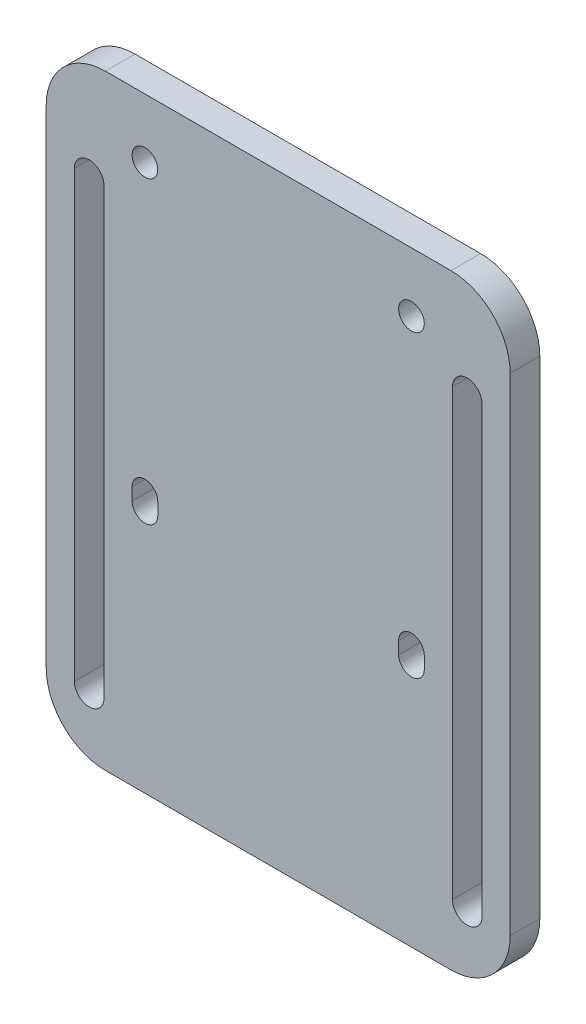
SolidWorks part; units mm, degrees
material "Acrylic (Medium-high impact)"
ref_plane "Спереди" through (0, 0, 0) normal (0, 0, 1) x (1, 0, 0)
ref_plane "Сверху" through (0, 0, 0) normal (0, 1, 0) x (1, 0, 0)
ref_plane "Справа" through (0, 0, 0) normal (1, 0, 0) x (0, 0, -1)
sketch "Model" plane through (0, 0, 0) normal (0, 0, 1) x (1, 0, 0)
  line L0 (0, 130.393) -> (0, -19.607) construction
  line L1 (38.3, 119.0065) -> (38.3, 3.8567) construction
  line L2 (39.6393, 110.7) -> (20.3566, 110.7) construction
  line L3 (27, 114.3973) -> (27, 106.7903) construction
  line L8 (27, 57.0366) -> (27, 46.0463) construction
  line L14 (-27, 114.3973) -> (-27, 106.7903) construction
  line L15 (-39.6393, 110.7) -> (-20.3566, 110.7) construction
  line L16 (-29.6, 50) -> (-29.6, 52.5)
  line L17 (-29.6, 52.5) -> (-29.6, 50)
  line L18 (-27, 57.0366) -> (-27, 46.0463) construction
  line L19 (-24.4, 52.5) -> (-24.4, 50)
  line L20 (-24.4, 50) -> (-24.4, 52.5)
  line L22 (-41.3, 12.5) -> (-41.3, 102.5)
  line L23 (-41.3, 102.5) -> (-41.3, 12.5)
  line L24 (-38.3, 119.0065) -> (-38.3, 3.8567) construction
  line L25 (-35.3, 102.5) -> (-35.3, 12.5)
  line L26 (-35.3, 12.5) -> (-35.3, 102.5)
  line L29 (-41.3, 12.5) -> (-35.3, 12.5) construction
  line L2974 (29.6, 52.5) -> (29.6, 50)
  line L2987 (24.4, 50) -> (24.4, 52.5)
  line L2994 (35.3, 12.5) -> (35.3, 102.5)
  line L3007 (41.3, 102.5) -> (41.3, 12.5)
  line L3504 (35, 0) -> (-35, 0)
  line L3511 (-47, 12) -> (-47, 110.7)
  line L3518 (-35, 122.7) -> (35, 122.7)
  line L3525 (47, 110.7) -> (47, 12)
  line L3777 (24.4, 52.5) -> (24.4, 50)
  line L3790 (29.6, 50) -> (29.6, 52.5)
  line L3887 (41.3, 12.5) -> (41.3, 102.5)
  line L3900 (35.3, 102.5) -> (35.3, 12.5)
  arc A0 (-47, 12) -> (-35, 0) centre (-35, 12) ccw
  arc A1 (35, 0) -> (47, 12) centre (35, 12) ccw
  arc A2 (47, 110.7) -> (35, 122.7) centre (35, 110.7) ccw
  arc A3 (-47, 110.7) -> (-35, 122.7) centre (-35, 110.7) cw
  circle A8 centre (27, 110.7) radius 2.6
  arc A9 (24.4, 52.5) -> (29.6, 52.5) centre (27, 52.5) cw
  arc A10 (24.4, 50) -> (29.6, 50) centre (27, 50) ccw
  arc A11 (35.3, 12.5) -> (41.3, 12.5) centre (38.3, 12.5) ccw
  arc A12 (35.3, 102.5) -> (41.3, 102.5) centre (38.3, 102.5) cw
  arc A17 (-35.3, 102.5) -> (-41.3, 102.5) centre (-38.3, 102.5) ccw
  circle A18 centre (-27, 110.7) radius 2.6
  arc A19 (-24.4, 50) -> (-29.6, 50) centre (-27, 50) cw
  arc A20 (-24.4, 52.5) -> (-29.6, 52.5) centre (-27, 52.5) ccw
  arc A22 (-35.3, 12.5) -> (-41.3, 12.5) centre (-38.3, 12.5) cw
  dimension "D1" = 12
  dimension "D17" = 5.2
  dimension "D22" = 2.6
  dimension "D23" = 2.6
  dimension "D26" = 90
  dimension "D2" = 70
  dimension "D3" = 122.7
  dimension "D4" = 38.3
  dimension "D5" = 58.2
  dimension "D6" = 11.3
  dimension "D19" = 11.3
  dimension "D20" = 2.5
  dimension "D21" = 5.2
  dimension "D24" = 50
  dimension "D25" = 6
  dimension "D27" = 12.5
extrude "Base" add sketch "Model" along normal blind 6 contours A3 L3511 A0 L3504 A1 L3525 A2 L3518 L25 A22 L22 A17 A20 L19 A19 L16 L2994 A12 L3007 A11 A8 A10 L2987 A9 L2974 region at (0, 61.6424, 0)
